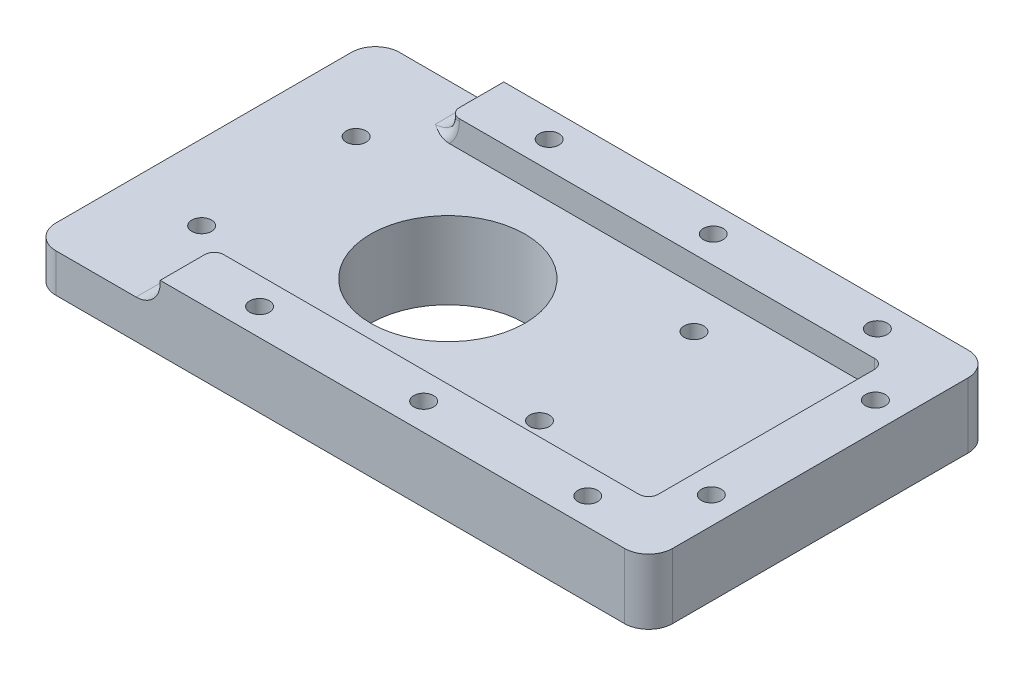
SolidWorks part; units mm, degrees
ref_plane "Front Plane" through (0, 0, 0) normal (0, 0, 1) x (1, 0, 0)
ref_plane "Top Plane" through (0, 0, 0) normal (0, 1, 0) x (1, 0, 0)
ref_plane "Right Plane" through (0, 0, 0) normal (1, 0, 0) x (0, 0, -1)
sketch "Sketch1" plane through (0, 0, 0) normal (0, 1, 0) x (1, 0, 0)
  line L0 (-21, 0) -> (21, 0) construction
  line L1 (-21, 11.5) -> (21, 11.5)
  line L2 (-21, 11.5) -> (-21, -11.5)
  line L3 (-21, -11.5) -> (21, -11.5)
  line L4 (21, 11.5) -> (21, -11.5)
  line L5 (-21, 11.5) -> (21, -11.5) construction
  line L6 (-21, -11.5) -> (21, 11.5) construction
  line L7 (0, 11.5) -> (0, -11.5) construction
  point P0 (0, 0)
  point P6 (-17.5, 8)
  point P12 (17.5, 8)
  point P14 (-17.5, -8)
  point P15 (17.5, -8)
  dimension "D1" = 42
  dimension "D2" = 23
  dimension "D3" = 3.5
  dimension "D4" = 3.5
  dimension "D5" = 35
extrude "Boss-Extrude1" add sketch "Sketch1" along normal blind 4
sketch "Sketch2" plane through (0, 4, 0) normal (0, 1, 0) x (1, 0, 0)
  line L1 (-25.3, 17.8) -> (25.3, 17.8)
  line L2 (-25.3, 17.8) -> (-25.3, -17.8)
  line L3 (-25.3, -17.8) -> (25.3, -17.8)
  line L4 (25.3, 17.8) -> (25.3, -17.8)
  line L5 (-25.3, 17.8) -> (25.3, -17.8) construction
  line L6 (-25.3, -17.8) -> (25.3, 17.8) construction
  line L7 (-25.3, 0) -> (25.3, 0)
  point P6 (0, 0)
  line M5 (21, -11.5) -> (21, 11.5)
  line M6 (21, 11.5) -> (-21, 11.5)
  line M7 (-21, 11.5) -> (-21, -11.5)
  line M8 (-21, -11.5) -> (21, -11.5)
  dimension "D1" = 35.6
  dimension "D2" = 50.6
extrude "Boss-Extrude2" add sketch "Sketch2" along normal blind 4 contours L2 L7 L4 L1 M7 M6 M5 | L7 M7 M5 M6 | L7 L2 L3 L4 M5 M8 M7 | L7 M7 M8 M5 region at (0, 4, -12.5426) region at (0, 4, 12.5426) region at (0, 4, -5.75) region at (0, 4, 5.75)
sketch "Sketch5" plane through (0, 8, 0) normal (0, 1, 0) x (1, 0, 0)
  circle A0 centre (0, 0) radius 8
  dimension "D1" = 16
extrude "Cut-Extrude1" cut sketch "Sketch5" against normal through all
sketch "Sketch6" plane through (0, 8, 0) normal (0, 1, 0) x (1, 0, 0)
  line L0 (-12, -999.5456) -> (-12, 49000.4544) construction
  line L1 (-1000, 0) -> (49000, 0) construction
  line L2 (-12, 12.2) -> (-12, 17.8)
  line L3 (-12, -12.2) -> (33, -12.2)
  line L4 (-12, -12.2) -> (-12, 12.2)
  line L5 (-12, 12.2) -> (33, 12.2)
  line L6 (33, -12.2) -> (33, 12.2)
  line L7 (-25.3, 17.8) -> (25.3, 17.8) construction
  line L8 (-12, 17.8) -> (38.6, 17.8)
  line L9 (-12, -12.2) -> (-12, -17.8)
  line L10 (-12, -17.8) -> (38.6, -17.8)
  line L11 (38.6, -17.8) -> (38.6, 17.8)
  line L12 (-25.3, -17.8) -> (25.3, -17.8) construction
  point P4 (-4.5, 15)
  point P6 (12.5, 15)
  point P7 (29.5, 15)
  point P8 (35.8, 8.5)
  point P9 (35.8, -8.5)
  point P10 (29.5, -15)
  point P11 (12.5, -15)
  point P12 (-4.5, -15)
  point P17 (33, 0)
  line M15 (-25.3, -17.8) -> (25.3, -17.8)
  line M16 (25.3, -17.8) -> (25.3, 17.8)
  line M17 (25.3, 17.8) -> (-25.3, 17.8)
  dimension "D1" = 12
  dimension "D2" = 7.5
  dimension "D3" = 17
  dimension "D4" = 17
  dimension "D5" = 15
  dimension "D6" = 8.5
  dimension "D7" = 35.8
  dimension "D8" = 24.4
  dimension "D9" = 45
  dimension "D10" = 5.6
extrude "Boss-Extrude3" add sketch "Sketch6" along normal blind 2.75 contours L2 L5 M16 M17 | L10 L11 L8 L5 L6 L3 M16 | L3 L9 M15 M16 region at (6.65, 8, -15) region at (6.65, 8, 15) region at (33.792, 8, 0)
sketch "Sketch7" plane through (25.3, 0, 0) normal (1, 0, 0) x (0, 0, -1)
  line L1 (-17.8, 8) -> (17.8, 8)
  line L2 (-17.8, 8) -> (-17.8, 4)
  line L3 (-17.8, 4) -> (17.8, 4)
  line L4 (17.8, 8) -> (17.8, 4)
extrude "Boss-Extrude4" add sketch "Sketch7" along normal up to surface (13.3 mm away) up to face at (38.6, 9.375, 0)
hole_wizard "M2.5x0.45 Tapped Hole2" positions "Sketch8" profile "Sketch9" tap size "M2.5x0.45" standard "ANSI Metric" end condition through all
sketch "Sketch8" plane through (0, 10.75, 0) normal (0, 1, 0) x (1, 0, 0)
  point P0 (12.5, 15)
  point P3 (-4.5, 15)
  point P6 (29.5, 15)
  point P9 (35.8, 8.5)
  point P12 (35.8, -8.5)
  point P15 (29.5, -15)
  point P18 (12.5, -15)
  point P21 (-4.5, -15)
  point P24 (-17.5, 8)
  point P27 (17.5, 8)
  point P30 (17.5, -8)
  point P33 (-17.5, -8)
sketch "Sketch9" plane through (12.5, 10.75, -15) normal (1, 0, 0) x (0, 0, 1)
  line L0 (0, 0) -> (0, 10.75)
  line L1 (0, 10.75) -> (1.025, 10.75)
  line L2 (1.025, 10.75) -> (1.025, 0)
  line L5 (1.025, 0) -> (0, 0)
  line L11 (0, -6.35) -> (0, 107.95) construction
  dimension "Thru Tap Drill Dia." = 2.05
  dimension "Thru Tap Drill Depth" = 10.75
cosmetic thread "Hole Thread5" parameters "D2"=2.5
cosmetic thread "Hole Thread6" parameters "D2"=2.5
cosmetic thread "Hole Thread7" parameters "D2"=2.5
cosmetic thread "Hole Thread8" parameters "D2"=2.5
cosmetic thread "Hole Thread9" parameters "D2"=2.5
cosmetic thread "Hole Thread10" parameters "D2"=2.5
cosmetic thread "Hole Thread11" parameters "D2"=2.5
cosmetic thread "Hole Thread12" parameters "D2"=2.5
cosmetic thread "Hole Thread13" parameters "D2"=2.5
cosmetic thread "Hole Thread14" parameters "D2"=2.5
cosmetic thread "Hole Thread15" parameters "D2"=2.5
cosmetic thread "Hole Thread16" parameters "D2"=2.5
fillet "Fillet1" radius 2.5 12 edges at (-25.3, 6, 17.8) (-25.3, 6, -17.8) (38.6, 7.375, -17.8) (21, 2, -11.5) (-21, 2, -11.5) (-21, 2, 11.5) (21, 2, 11.5) (38.6, 7.375, 17.8) (-21, 4, 0) (21, 4, 0) (-12, 8, 15) (-12, 8, -15) tangent propagation no
fillet "Fillet2" radius 1 12 edges at (15.4199, 3.7766, -11.5) (-15.4199, 3.7766, -11.5) (-15.4199, 3.7766, 11.5) (15.4199, 3.7766, 11.5) (-12, 10.625, -12.2) (-12, 10.625, 12.2) (0, 4, -11.5) (0, 4, 11.5) (-12.7322, 8.7322, -12.2) (-12.7322, 8.7322, 12.2) (33, 9.375, 12.2) (33, 9.375, -12.2)
